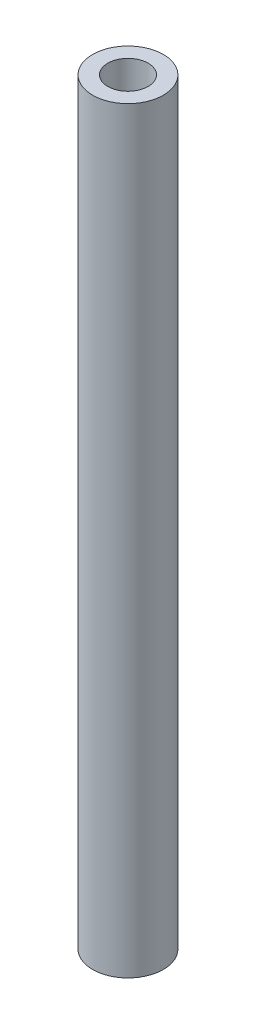
SolidWorks part; units mm, degrees
ref_plane "Plano frontal" through (0, 0, 0) normal (0, 0, 1) x (1, 0, 0)
ref_plane "Plano superior" through (0, 0, 0) normal (0, 1, 0) x (1, 0, 0)
ref_plane "Plano direito" through (0, 0, 0) normal (1, 0, 0) x (0, 0, -1)
ref_plane "Plano1" through (0, 0, 0) normal (0, 0, -1) x (-1, 0, 0)
sketch "Esboço1" plane through (0, 0, 0) normal (0, 0, -1) x (-1, 0, 0)
  line L0 (53.2146, -75) -> (54.7146, -75)
  line L1 (54.7146, -75) -> (54.7146, 0)
  line L2 (54.7146, 0) -> (53.2146, 0)
  line L3 (53.2146, 0) -> (53.2146, -75)
  line L4 (56.7146, -75) -> (56.7146, 0) construction
  dimension "D1" = 2
  dimension "D2" = 3.5
  dimension "D3" = 75
revolve "Revolução1" add sketch "Esboço1" angle 360 about L4 reverse direction yes
